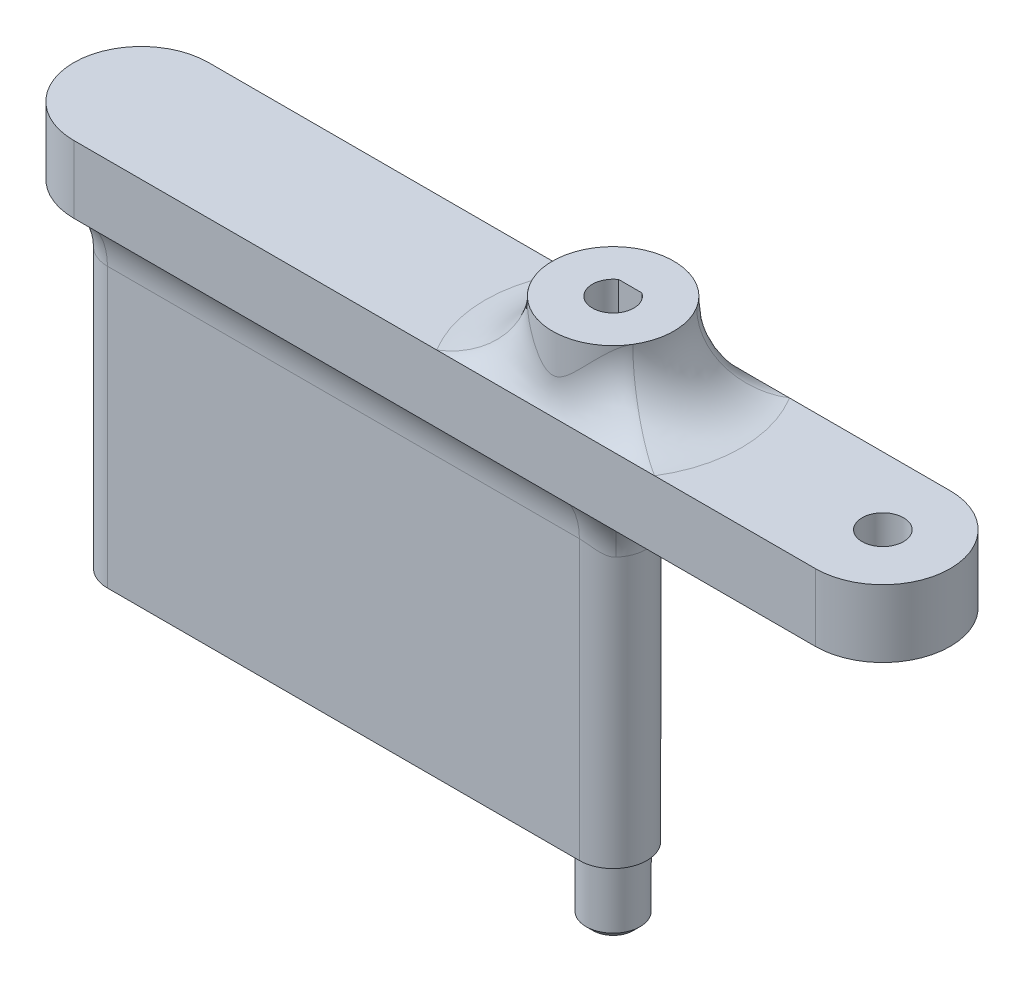
SolidWorks part; units mm, degrees
material "PET"
ref_plane "Front Plane" through (0, 0, 0) normal (0, 0, 1) x (1, 0, 0)
ref_plane "Top Plane" through (0, 0, 0) normal (0, 1, 0) x (1, 0, 0)
ref_plane "Right Plane" through (0, 0, 0) normal (1, 0, 0) x (0, 0, -1)
sketch "Sketch1" plane through (0, 0, 0) normal (0, 1, 0) x (1, 0, 0)
  line L0 (0, 0) -> (-70, 0) construction
  line L1 (0, -5) -> (-70, -5)
  line L2 (0, 5) -> (-70, 5)
  arc A0 (0, -5) -> (0, 5) centre (0, 0) ccw
  arc A1 (-70, 5) -> (-70, -5) centre (-70, 0) ccw
  point P3 (-35, 0)
  dimension "D1" = 70
  dimension "D2" = 10
extrude "Boss-Extrude1" add sketch "Sketch1" against normal blind 50
sketch "Sketch2" plane through (0, 0, 0) normal (0, 1, 0) x (1, 0, 0)
  line L0 (0, 0) -> (-70, 0) construction
  line L5 (0, -10) -> (-70, -10)
  line L6 (0, 10) -> (-70, 10)
  line L7 (0, 0) -> (40, 0) construction
  line L8 (0, 10) -> (40, 10)
  line L9 (0, -10) -> (40, -10)
  arc A5 (-70, 10) -> (-70, -10) centre (-70, 0) ccw
  arc A7 (40, -10) -> (40, 10) centre (40, 0) ccw
  circle A8 centre (40, 0) radius 3.075
  dimension "D5" = 6.15
  dimension "D7" = 10
  dimension "D1" = 70
  dimension "D2" = 20
  dimension "D3" = 20
  dimension "D4" = 40
  dimension "D6" = 70
extrude "Boss-Extrude2" add sketch "Sketch2" along normal blind 10
fillet "Fillet1" radius 10 1 edges at (5, 0, 0)
sketch "Sketch3" plane through (0, 10, 0) normal (0, 1, 0) x (1, 0, 0)
  circle A0 centre (0, 0) radius 9
  dimension "D1" = 18
extrude "Boss-Extrude3" add sketch "Sketch3" along normal blind 10
fillet "Fillet2" radius 10 1 edges at (0, 10, 9)
sketch "Sketch7" plane through (0, -50, 0) normal (0, -1, 0) x (1, 0, 0)
  circle A0 centre (0, 0) radius 4
  dimension "D1" = 8
extrude "Boss-Extrude4" add sketch "Sketch7" along normal blind 10
chamfer "Chamfer1" distance 1 angle 45 1 edges at (0, -60, -4)
sketch "Sketch8" plane through (0, 20, 0) normal (0, 1, 0) x (1, 0, 0)
  line L0 (1.7185, 2.55) -> (-1.7185, 2.55)
  arc A0 (-1.7185, 2.55) -> (1.7185, 2.55) centre (0, 0) ccw
  dimension "D1" = 6.15
  dimension "D2" = 2.55
extrude "Cut-Extrude1" cut sketch "Sketch8" against normal blind 12.15
